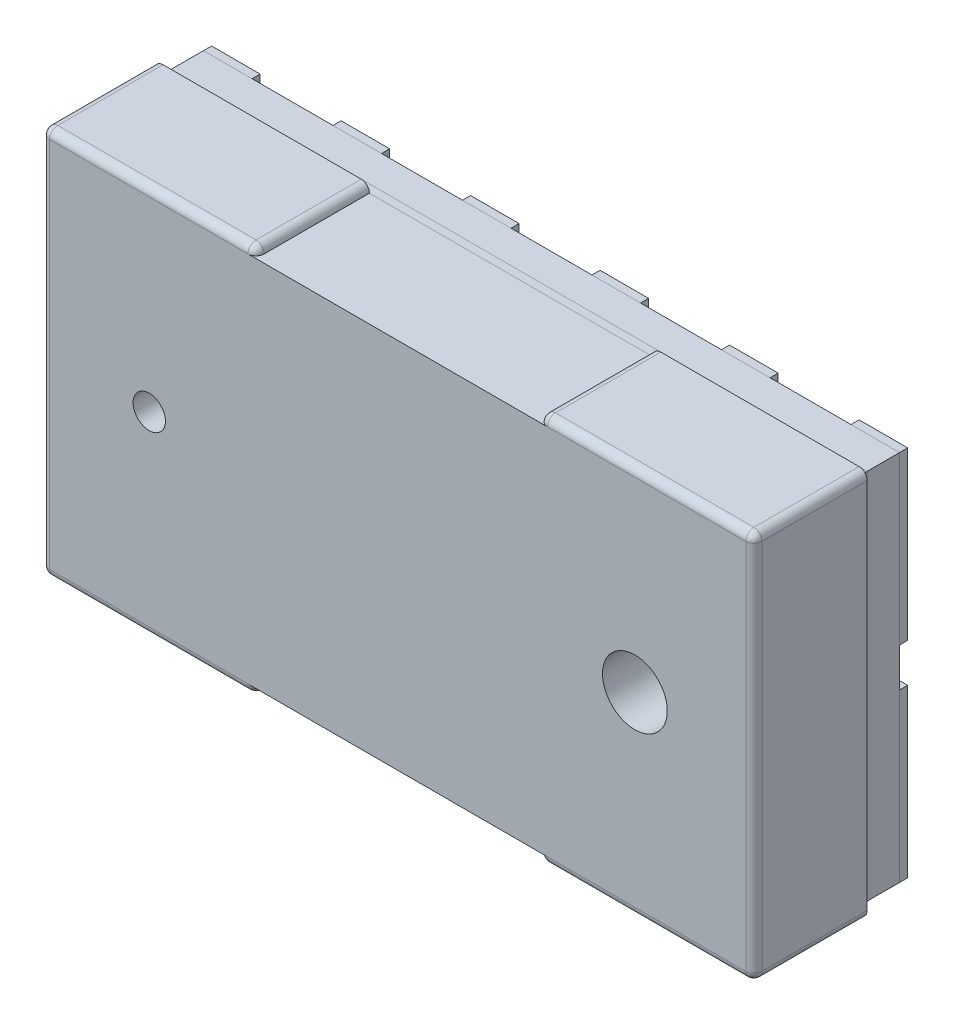
SolidWorks part; units mm, degrees
ref_plane "Plan de face" through (0, 0, 0) normal (0, 0, 1) x (1, 0, 0)
ref_plane "Plan de dessus" through (0, 0, 0) normal (0, 1, 0) x (1, 0, 0)
ref_plane "Plan de droite" through (0, 0, 0) normal (1, 0, 0) x (0, 0, -1)
sketch "Sketch1" plane through (0, 0, 0) normal (0, 0, 1) x (1, 0, 0)
  line L1 (2.15, 1.15) -> (-2.15, 1.15)
  line L2 (2.15, 1.15) -> (2.15, -1.15)
  line L3 (2.15, -1.15) -> (-2.15, -1.15)
  line L4 (-2.15, 1.15) -> (-2.15, -1.15)
  line L5 (2.15, 1.15) -> (-2.15, -1.15) construction
  line L6 (2.15, -1.15) -> (-2.15, 1.15) construction
  point P0 (0, 0)
  dimension "D1" = 2.3
  dimension "D2" = 4.3
extrude "Boss-Extrude1" add sketch "Sketch1" along normal blind 0.05
sketch "Sketch2" plane through (0, 0, 0.05) normal (0, 0, 1) x (1, 0, 0)
  line L4 (-2.15, 1.15) -> (-2.15, -1.15)
  line L5 (-2.15, -1.15) -> (2.15, -1.15)
  line L6 (2.15, -1.15) -> (2.15, 1.15)
  line L7 (2.15, 1.15) -> (-2.15, 1.15)
  line L8 (-2.15, 1.15) -> (-2.15, -1.15)
  line L9 (-2.15, -1.15) -> (2.15, -1.15)
  line L10 (2.15, -1.15) -> (2.15, 1.15)
  line L11 (2.15, 1.15) -> (-2.15, 1.15)
  dimension "D1" = 0
extrude "Boss-Extrude2" add sketch "Sketch2" along normal blind 0.2 separate body
sketch "Sketch3" plane through (0, 0, 0.25) normal (0, 0, 1) x (1, 0, 0)
  line L4 (2.15, 1.15) -> (-2.15, 1.15)
  line L5 (-2.15, 1.15) -> (-2.15, -1.15)
  line L6 (-2.15, -1.15) -> (2.15, -1.15)
  line L7 (2.15, -1.15) -> (2.15, 1.15)
  line L8 (2.15, 1.15) -> (-2.15, 1.15)
  line L9 (-2.15, 1.15) -> (-2.15, -1.15)
  line L10 (-2.15, -1.15) -> (2.15, -1.15)
  line L11 (2.15, -1.15) -> (2.15, 1.15)
  dimension "D1" = 0
extrude "Boss-Extrude3" add sketch "Sketch3" along normal blind 0.05 separate body
sketch "Sketch4" plane through (0, 0, 0.3) normal (0, 0, 1) x (1, 0, 0)
  line L1 (-2.2, -1.2) -> (2.2, -1.2)
  line L2 (-2.2, -1.2) -> (-2.2, 1.2)
  line L3 (-2.2, 1.2) -> (2.2, 1.2)
  line L4 (2.2, -1.2) -> (2.2, 1.2)
  line L5 (-2.2, -1.2) -> (2.2, 1.2) construction
  line L6 (-2.2, 1.2) -> (2.2, -1.2) construction
  point P0 (0, 0)
  dimension "D1" = 2.4
  dimension "D2" = 4.4
extrude "Boss-Extrude4" add sketch "Sketch4" along normal blind 0.7 separate body
fillet "Fillet3" radius 0.05 4 edges at (0, -1.2, 1) (-2.2, 0, 1) (0, 1.2, 1) (2.2, 0, 1)
sketch "Sketch6" plane through (0, 0, 1) normal (0, 0, 1) x (1, 0, 0)
  line L0 (2.2, 1.2) -> (-2.2, 1.2) construction
  line L1 (-0.875, 1.15) -> (0.875, 1.15)
  line L2 (-0.875, 1.15) -> (-0.875, 1.25)
  line L3 (-0.875, 1.25) -> (0.875, 1.25)
  line L4 (0.875, 1.15) -> (0.875, 1.25)
  line L5 (-0.875, 1.15) -> (0.875, 1.25) construction
  line L6 (-0.875, 1.25) -> (0.875, 1.15) construction
  line L12 (0.55, 0) -> (-0.55, 0) construction
  line L13 (-0.875, -1.25) -> (0.875, -1.15) construction
  line L14 (-0.875, -1.15) -> (0.875, -1.25) construction
  line L15 (0.875, -1.15) -> (0.875, -1.25)
  line L16 (-0.875, -1.25) -> (0.875, -1.25)
  line L17 (-0.875, -1.15) -> (-0.875, -1.25)
  line L18 (-0.875, -1.15) -> (0.875, -1.15)
  point P0 (0, 1.2)
  point P13 (0, -1.2)
  dimension "D1" = 1.75
  dimension "D2" = 0.05
extrude "Cut-Extrude1" cut sketch "Sketch6" against normal blind 0.7
fillet "Fillet1" radius 0.05 16 edges at (2.2, 1.2, 0.625) (2.2, -1.2, 0.625) (0.875, -1.2, 0.625) (-0.875, -1.2, 0.625) (-2.2, 1.2, 0.625) (-0.875, 1.2, 0.625) (0.875, 1.2, 0.625) (-2.2, -1.2, 0.625) (2.1854, 1.1854, 0.9854) (2.1854, -1.1854, 0.9854) (0.875, -1.1854, 0.9854) (-0.875, -1.1854, 0.9854) (-2.1854, 1.1854, 0.9854) (-0.875, 1.1854, 0.9854) (0.875, 1.1854, 0.9854) (-2.1854, -1.1854, 0.9854)
sketch "Sketch7" plane through (0, 0, 1) normal (0, 0, 1) x (1, 0, 0)
  line L0 (-1.535, 0) -> (1.465, 0) construction
  line L2 (-2.2, -1.15) -> (-2.2, 1.15) construction
  circle A0 centre (-1.535, 0) radius 0.1
  circle A1 centre (1.465, 0) radius 0.2
  dimension "D1" = 0.4
  dimension "D2" = 0.2
  dimension "D3" = 3
  dimension "D4" = 0.665
extrude "Cut-Extrude2" cut sketch "Sketch7" against normal blind 0.7
sketch "Sketch8" plane through (0, 0, 0) normal (0, 0, -1) x (-1, 0, 0)
  line L0 (-1.05, -1.05) -> (-1.05, -0.55)
  line L1 (-1.85, -1.05) -> (-1.35, -1.05)
  line L2 (-1.85, -1.05) -> (-1.85, -0.8)
  line L3 (-1.85, -0.55) -> (-1.35, -0.55)
  line L4 (-1.35, -1.05) -> (-1.35, -0.55)
  line L5 (-1.05, -1.05) -> (-0.55, -1.05)
  line L6 (-0.55, -1.05) -> (-0.55, -0.55)
  line L7 (-1.05, -0.55) -> (-0.55, -0.55)
  line L8 (-0.25, -1.05) -> (-0.25, -0.55)
  line L9 (-0.25, -1.05) -> (0.25, -1.05)
  line L10 (0.25, -1.05) -> (0.25, -0.55)
  line L11 (-0.25, -0.55) -> (0.25, -0.55)
  line L12 (0.55, -1.05) -> (0.55, -0.55)
  line L13 (0.55, -1.05) -> (1.05, -1.05)
  line L14 (1.05, -1.05) -> (1.05, -0.55)
  line L15 (0.55, -0.55) -> (1.05, -0.55)
  line L16 (1.35, -1.05) -> (1.35, -0.55)
  line L17 (1.35, -1.05) -> (1.85, -1.05)
  line L18 (1.85, -1.05) -> (1.85, -0.55)
  line L19 (1.35, -0.55) -> (1.85, -0.55)
  line L20 (-1.05, -0.25) -> (-1.05, 0.25) [skipped]
  line L21 (-1.05, -0.25) -> (-0.55, -0.25) [skipped]
  line L22 (-0.55, -0.25) -> (-0.55, 0.25) [skipped]
  line L23 (-1.05, 0.25) -> (-0.55, 0.25) [skipped]
  line L24 (-0.25, -0.25) -> (-0.25, 0.25) [skipped]
  line L25 (-0.25, -0.25) -> (0.25, -0.25) [skipped]
  line L26 (0.25, -0.25) -> (0.25, 0.25) [skipped]
  line L27 (-0.25, 0.25) -> (0.25, 0.25) [skipped]
  line L28 (0.55, -0.25) -> (0.55, 0.25) [skipped]
  line L29 (0.55, -0.25) -> (1.05, -0.25) [skipped]
  line L30 (1.05, -0.25) -> (1.05, 0.25) [skipped]
  line L31 (0.55, 0.25) -> (1.05, 0.25) [skipped]
  line L32 (1.35, -0.25) -> (1.35, 0.25)
  line L33 (1.35, -0.25) -> (1.85, -0.25)
  line L34 (1.85, -0.25) -> (1.85, 0.25)
  line L35 (1.35, 0.25) -> (1.85, 0.25)
  line L36 (-1.05, 0.55) -> (-1.05, 1.05)
  line L37 (-1.05, 0.55) -> (-0.55, 0.55)
  line L38 (-0.55, 0.55) -> (-0.55, 1.05)
  line L39 (-1.05, 1.05) -> (-0.55, 1.05)
  line L40 (-0.25, 0.55) -> (-0.25, 1.05)
  line L41 (-0.25, 0.55) -> (0.25, 0.55)
  line L42 (0.25, 0.55) -> (0.25, 1.05)
  line L43 (-0.25, 1.05) -> (0.25, 1.05)
  line L44 (0.55, 0.55) -> (0.55, 1.05)
  line L45 (0.55, 0.55) -> (1.05, 0.55)
  line L46 (1.05, 0.55) -> (1.05, 1.05)
  line L47 (0.55, 1.05) -> (1.05, 1.05)
  line L48 (1.35, 0.55) -> (1.35, 1.05)
  line L49 (1.35, 0.55) -> (1.85, 0.55)
  line L50 (1.85, 0.55) -> (1.85, 1.05)
  line L51 (1.35, 1.05) -> (1.85, 1.05)
  line L52 (-1.85, -0.25) -> (-1.85, 0.25)
  line L53 (-1.85, -0.25) -> (-1.35, -0.25)
  line L54 (-1.35, -0.25) -> (-1.35, 0.25)
  line L55 (-1.85, 0.25) -> (-1.35, 0.25)
  line L56 (-1.85, 0.55) -> (-1.85, 1.05)
  line L57 (-1.85, 0.55) -> (-1.35, 0.55)
  line L58 (-1.35, 0.55) -> (-1.35, 1.05)
  line L59 (-1.85, 1.05) -> (-1.35, 1.05)
  line L60 (-1.85, -1.05) -> (-1.05, -1.05) construction
  line L61 (-1.85, -1.05) -> (-1.85, -0.8) construction
  line L62 (-1.35, 0.55) -> (1.35, -0.55) construction
  line L63 (1.35, 0.55) -> (-1.35, -0.55) construction
  line L64 (-1.85, -0.8) -> (-1.85, -0.55) construction
  line L65 (-1.85, -0.55) -> (-1.93, -0.55)
  line L66 (-1.85, -0.55) -> (-1.85, -0.8) construction
  line L67 (-1.85, -0.8) -> (-1.93, -0.8)
  line L68 (-1.93, -0.55) -> (-1.93, -0.8)
  line L69 (-1.85, -0.55) -> (-1.85, -0.25) construction
  line L70 (-1.85, -0.8) -> (-1.85, -0.55) construction
  point P4 (-1.3512, -0.55)
  dimension "D1" = 0.5
  dimension "D2" = 5
  dimension "D4" = 0.8
  dimension "D5" = 0.8
  dimension "D6" = 0.25
  dimension "D7" = 0.08
  dimension "D8" = 0.5
  dimension "D3" = 3
sketch "Sketch9" plane through (0, 0, 0) normal (0, 0, -1) x (-1, 0, 0)
  line L0 (-2.15, 1.15) -> (2.15, 1.15) construction
  line L1 (-1.85, 0.55) -> (-1.35, 0.55)
  line L2 (-1.85, 0.55) -> (-1.85, 1.15)
  line L3 (-1.85, 1.15) -> (-1.35, 1.15)
  line L4 (-1.35, 0.55) -> (-1.35, 1.15)
  line L5 (-1.05, 0.55) -> (-0.55, 0.55)
  line L6 (-1.05, 0.55) -> (-1.05, 1.15)
  line L7 (-1.05, 1.15) -> (-0.55, 1.15)
  line L8 (-0.55, 0.55) -> (-0.55, 1.15)
  line L9 (-0.25, 0.55) -> (0.25, 0.55)
  line L10 (-0.25, 0.55) -> (-0.25, 1.15)
  line L11 (-0.25, 1.15) -> (0.25, 1.15)
  line L12 (0.25, 0.55) -> (0.25, 1.15)
  line L13 (0.55, 0.55) -> (1.05, 0.55)
  line L14 (0.55, 0.55) -> (0.55, 1.15)
  line L15 (0.55, 1.15) -> (1.05, 1.15)
  line L16 (1.05, 0.55) -> (1.05, 1.15)
  line L17 (1.35, 0.55) -> (1.85, 0.55)
  line L18 (1.35, 0.55) -> (1.35, 1.15)
  line L19 (1.35, 1.15) -> (1.85, 1.15)
  line L20 (1.85, 0.55) -> (1.85, 1.15)
  line L21 (-1.85, 0.55) -> (-1.05, 0.55) construction
  line L22 (2.15, -1.15) -> (-2.15, -1.15) construction
  line L23 (-1.85, -0.55) -> (-1.35, -0.55)
  line L24 (-1.85, -0.8) -> (-1.85, -1.15)
  line L25 (-1.85, -1.15) -> (-1.35, -1.15)
  line L26 (-1.35, -0.55) -> (-1.35, -1.15)
  line L27 (-1.05, -0.55) -> (-1.05, -1.15)
  line L28 (-1.05, -0.55) -> (-0.55, -0.55)
  line L29 (-0.55, -0.55) -> (-0.55, -1.15)
  line L30 (-1.05, -1.15) -> (-0.55, -1.15)
  line L31 (-0.25, -0.55) -> (-0.25, -1.15)
  line L32 (-0.25, -0.55) -> (0.25, -0.55)
  line L33 (0.25, -0.55) -> (0.25, -1.15)
  line L34 (-0.25, -1.15) -> (0.25, -1.15)
  line L35 (0.55, -0.55) -> (0.55, -1.15)
  line L36 (0.55, -0.55) -> (1.05, -0.55)
  line L37 (1.05, -0.55) -> (1.05, -1.15)
  line L38 (0.55, -1.15) -> (1.05, -1.15)
  line L39 (1.35, -0.55) -> (1.35, -1.15)
  line L40 (1.35, -0.55) -> (1.85, -0.55)
  line L41 (1.85, -0.55) -> (1.85, -1.15)
  line L42 (1.35, -1.15) -> (1.85, -1.15)
  line L43 (-1.85, -0.55) -> (-1.05, -0.55) construction
  line L44 (-1.85, -0.25) -> (-1.85, 0.25) construction
  line L45 (-1.85, -0.25) -> (-1.35, -0.25) construction
  line L46 (-1.35, -0.25) -> (-1.35, 0.25) construction
  line L47 (-1.85, 0.25) -> (-1.35, 0.25) construction
  line L48 (-1.85, -0.25) -> (-1.85, 0.25)
  line L49 (-1.85, -0.25) -> (-1.35, -0.25)
  line L50 (-1.35, -0.25) -> (-1.35, 0.25)
  line L51 (-1.85, 0.25) -> (-1.35, 0.25)
  line L52 (1.35, -0.25) -> (1.35, 0.25) construction
  line L53 (1.35, -0.25) -> (1.85, -0.25) construction
  line L54 (1.85, -0.25) -> (1.85, 0.25) construction
  line L55 (1.35, 0.25) -> (1.85, 0.25) construction
  line L56 (1.35, -0.25) -> (1.35, 0.25)
  line L57 (1.35, -0.25) -> (1.85, -0.25)
  line L58 (1.85, -0.25) -> (1.85, 0.25)
  line L59 (1.35, 0.25) -> (1.85, 0.25)
  line L60 (-2.15, -1.15) -> (-2.15, 1.15) construction
  line L61 (-1.93, -0.55) -> (-1.85, -0.55)
  line L62 (-1.93, -0.55) -> (-1.93, -0.8)
  line L63 (-1.93, -0.8) -> (-1.85, -0.8)
  line L65 (-2.15, 0.12) -> (-2.05, 0.12)
  line L66 (-2.15, 0.12) -> (-2.15, -0.12)
  line L67 (-2.15, -0.12) -> (-2.05, -0.12)
  line L68 (-2.05, 0.12) -> (-2.05, -0.12)
  line L69 (0, 0.55) -> (0, -0.55) construction
  line L70 (2.05, 0.12) -> (2.05, -0.12)
  line L71 (2.15, -0.12) -> (2.05, -0.12)
  line L72 (2.15, 0.12) -> (2.15, -0.12)
  line L73 (2.15, 0.12) -> (2.05, 0.12)
  point P71 (-2.05, 0)
  dimension "D1" = 5
  dimension "D2" = 0.8
  dimension "D3" = 5
  dimension "D4" = 0.8
  dimension "D5" = 0.1
  dimension "D6" = 0.24
extrude "Cut-Extrude3" cut sketch "Sketch9" against normal through all
extrude "Boss-Extrude5" add sketch "Sketch8" against normal up to surface (0.05 mm away) separate body up to face at (0, 0, 0.05)
